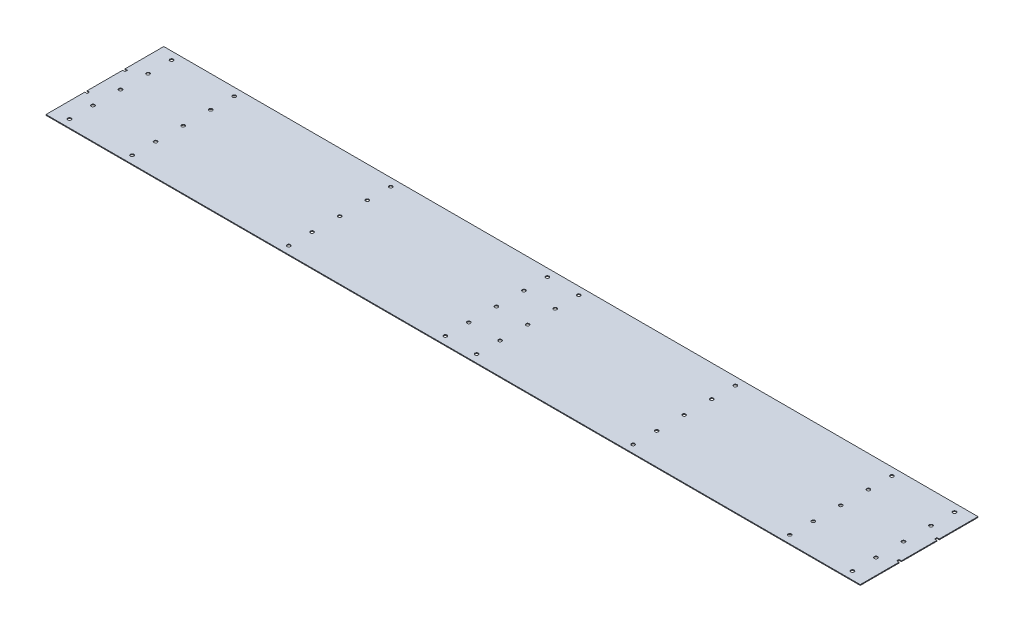
SolidWorks part; units mm, degrees
ref_plane "Front Plane" through (0, 0, 0) normal (0, 0, 1) x (1, 0, 0)
ref_plane "Top Plane" through (0, 0, 0) normal (0, 1, 0) x (1, 0, 0)
ref_plane "Right Plane" through (0, 0, 0) normal (1, 0, 0) x (0, 0, -1)
sketch "Sketch1" plane through (0, 0, 0) normal (0, 1, 0) x (1, 0, 0)
  line L0 (-500, -25.7) -> (-500, -75.2)
  line L1 (-500, -75.2) -> (540, -75.2)
  line L2 (540, -75.2) -> (540, -25.7)
  line L3 (540, -25.7) -> (-500, -25.7) construction
  line L4 (0, 0) -> (-497, 0) construction
  line L5 (-500, -25.7) -> (-497, -25.7)
  line L7 (-497, 25.7) -> (-500, 25.7)
  line L8 (-500, 25.7) -> (-500, 75.2)
  line L9 (-500, 75.2) -> (540, 75.2)
  line L10 (540, 75.2) -> (540, 25.7)
  line L11 (540, 25.7) -> (537, 25.7)
  line L13 (537, -25.7) -> (540, -25.7)
  line L14 (0, 35.2) -> (520, 35.2) construction
  line L15 (-497, 25.7) -> (-497, 22.7)
  line L16 (-497, 25.7) -> (537, 25.7) construction
  line L17 (537, 25.7) -> (537, -25.7) construction
  line L18 (-497, 25.7) -> (-497, -25.7) construction
  line L19 (-497, 22.7) -> (-500, 22.7)
  line L20 (-500, 22.7) -> (-500, -22.7)
  line L21 (-500, -22.7) -> (-497, -22.7)
  line L22 (-497, -22.7) -> (-497, -25.7)
  line L23 (537, 25.7) -> (537, 22.7)
  line L24 (537, 22.7) -> (540, 22.7)
  line L25 (540, 22.7) -> (540, -22.7)
  line L26 (540, -22.7) -> (537, -22.7)
  line L27 (537, -22.7) -> (537, -25.7)
  line L28 (540, 0) -> (537, 0) construction
  line L29 (520, 35.2) -> (520, -35.2) construction
  line L30 (-497, 0) -> (-500, 0) construction
  line L31 (0, 35.2) -> (0, -35.2) construction
  line L32 (520, -35.2) -> (0, -35.2) construction
  line L33 (0, 35.2) -> (0, 65.2) construction
  line L34 (0, 65.2) -> (520, 65.2) construction
  line L35 (520, 65.2) -> (520, 35.2) construction
  line L36 (520, -35.2) -> (520, -65.2) construction
  line L37 (520, -65.2) -> (0, -65.2) construction
  line L38 (0, -65.2) -> (0, -35.2) construction
  line L39 (0, 0) -> (520, 0) construction
  line L40 (-200, 65.2) -> (-200, 35.2) construction
  line L41 (-200, 35.2) -> (-200, 0) construction
  line L42 (-200, 0) -> (-200, -35.2) construction
  line L43 (-200, -35.2) -> (-200, -65.2) construction
  line L44 (40, 65.2) -> (40, -65.2) construction
  line L45 (-400, 65.2) -> (-480, 65.2) construction
  line L46 (-480, 65.2) -> (-480, -65.2) construction
  line L47 (-480, -65.2) -> (-400, -65.2) construction
  line L48 (-400, -65.2) -> (-400, 65.2) construction
  line L49 (-400, 65.2) -> (0, 65.2) construction
  line L50 (440, 65.2) -> (440, -65.2) construction
  line L51 (-400, 35.2) -> (0, 35.2) construction
  line L52 (440, -65.2) -> (520, -65.2) construction
  line L53 (-400, -35.2) -> (0, -35.2) construction
  line L55 (-480, -65.2) -> (0, -65.2) construction
  line L56 (440, -35.2) -> (520, -35.2) construction
  line L58 (440, 0) -> (520, 0) construction
  line L60 (440, 35.2) -> (520, 35.2) construction
  line L62 (440, 65.2) -> (520, 65.2) construction
  circle A0 centre (0, -35.2) radius 2.15
  circle A30 centre (0, 35.2) radius 2.15
  circle A31 centre (0, -65.2) radius 2.15
  circle A32 centre (0, 65.2) radius 2.15
  circle A33 centre (-200, -65.2) radius 2.15
  circle A34 centre (-200, -35.2) radius 2.15
  circle A35 centre (-200, 35.2) radius 2.15
  circle A36 centre (-200, 65.2) radius 2.15
  circle A53 centre (0, 0) radius 2.15
  circle A55 centre (-200, 0) radius 2.15
  circle A56 centre (-400, 0) radius 2.15
  circle A57 centre (-400, -65.2) radius 2.15
  circle A58 centre (-400, -35.2) radius 2.15
  circle A59 centre (-400, 35.2) radius 2.15
  circle A60 centre (-400, 65.2) radius 2.15
  circle A61 centre (40, -65.2) radius 2.15
  circle A62 centre (40, -35.2) radius 2.15
  circle A63 centre (40, 0) radius 2.15
  circle A64 centre (40, 35.2) radius 2.15
  circle A65 centre (40, 65.2) radius 2.15
  circle A66 centre (520, 65.2) radius 2.15
  circle A67 centre (520, 35.2) radius 2.15
  circle A68 centre (520, 0) radius 2.15
  circle A69 centre (520, -35.2) radius 2.15
  circle A70 centre (520, -65.2) radius 2.15
  circle A71 centre (240, -65.2) radius 2.15
  circle A72 centre (240, -35.2) radius 2.15
  circle A73 centre (240, 0) radius 2.15
  circle A74 centre (240, 35.2) radius 2.15
  circle A75 centre (240, 65.2) radius 2.15
  circle A76 centre (440, -65.2) radius 2.15
  circle A77 centre (440, -35.2) radius 2.15
  circle A78 centre (440, 0) radius 2.15
  circle A79 centre (440, 35.2) radius 2.15
  circle A80 centre (440, 65.2) radius 2.15
  circle A81 centre (-480, 65.2) radius 2.15
  circle A82 centre (-480, 35.2) radius 2.15
  circle A83 centre (-480, 0) radius 2.15
  circle A84 centre (-480, -65.2) radius 2.15
  circle A85 centre (-480, -35.2) radius 2.15
  dimension "D12" = 4.3
  dimension "D13" = 12.5
  dimension "D11" = 200
  dimension "D2" = 45.4
  dimension "D3" = 3
  dimension "D6" = 10
  dimension "D7" = 30
  dimension "D16" = 12.5
  dimension "D8" = 3
  dimension "D4" = 40
  dimension "D17" = 200
  dimension "D5" = 80
  dimension "D15" = 20
  dimension "D18" = 80
  dimension "D19" = 20
  dimension "D20" = 1040
  dimension "D9" = 3
  dimension "D14" = 3
  dimension "D10" = 3
extrude "Boss-Extrude1" add sketch "Sketch1" along normal blind 1 contours L27 L26 L25 L24 L23 L11 L10 L9 L8 L7 L15 L19 L20 L21 L22 L5 L0 L1 L2 L13 A59 A60 A58 A74 A53 A36 A35 A34 A33 A32 A31 A30 A0 region at (20, 0, 0)
equation "\"skin_sheetmetal_thickness\"= 0.80"
equation "\"base_width_skin_spacer\" = \"base_width_skin_target_width\" - 4 * \"skin_sheetmetal_thickness\" - 2 * \"base_width_skin_target_bend_radius\""
equation "\"base_width_skin_inner\" = \"base_width_skin_spacer\" + 2 * \"skin_sheetmetal_thickness\""
equation "\"base_width_skin_outer\" = \"base_width_skin_inner\" + 2 * \"skin_sheetmetal_thickness\""
equation "\"bend_cut_width\"= 3"
equation "\"bend_cut_length\"= 3"
equation "\"bend_offset_inner\"= 12.5"
equation "\"bend_offset_outer\" = \"bend_offset_inner\" + \"skin_sheetmetal_thickness\""
equation "\"border_offset_ends\"= 20"
equation "\"border_offset_sides\"= 10"
equation "\"border_offset_flange_horiz\"= 10"
equation "\"rivet_size\"= 4.3"
equation "\"rivet_offset_ends\"= \"rivet_spacing_horiz\"/2 - \"border_offset_ends\""
equation "\"rivet_spacing_horiz\"= 200"
equation "\"rivet_spacing_vert\"= 30"
equation "\"rivet_spacing_offset_right\"= 40"
equation "\"base_length\"= 200"
equation "\"base_width_skin_spacer_length\" = 315"
equation "\"bend_offset_spacer_tab\"= 21.0"
equation "\"D2@Sketch1\"=\"base_width_skin_inner\""
equation "\"D3@Sketch1\"=\"bend_cut_length\""
equation "\"D8@Sketch1\"=\"bend_cut_width\""
equation "\"D16@Sketch1\"=\"bend_offset_inner\""
equation "\"D7@Sketch1\"=\"rivet_spacing_vert\""
equation "\"D12@Sketch1\"=\"rivet_size\""
equation "\"D6@Sketch1\"=\"border_offset_flange_horiz\""
equation "\"D11@Sketch1\"=\"rivet_spacing_horiz\""
equation "\"D4@Sketch1\"=\"rivet_spacing_offset_right\""
equation "\"D17@Sketch1\"=\"rivet_spacing_horiz\""
equation "\"D5@Sketch1\"=\"rivet_offset_ends\""
equation "\"D15@Sketch1\"=\"border_offset_ends\""
equation "\"D18@Sketch1\"=\"rivet_offset_ends\""
equation "\"D19@Sketch1\"=\"border_offset_ends\""
equation "\"base_width_skin_target_width\" = 50"
equation "\"base_width_skin_target_bend_radius\" = 1.5"
